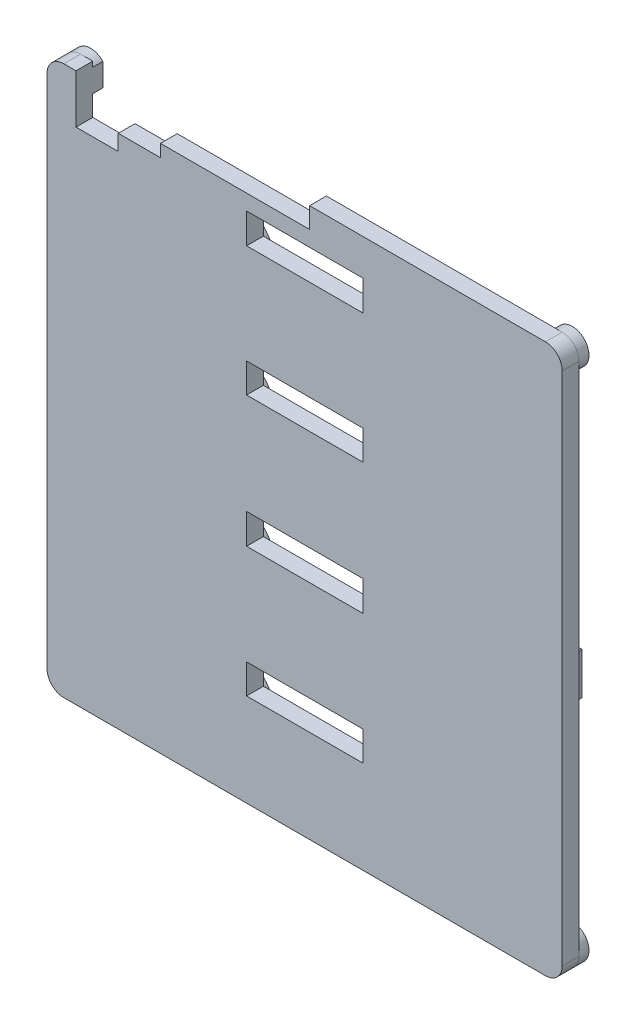
SolidWorks part; units mm, degrees
ref_plane "前视基准面" through (0, 0, 0) normal (0, 0, 1) x (1, 0, 0)
ref_plane "上视基准面" through (0, 0, 0) normal (0, 1, 0) x (1, 0, 0)
ref_plane "右视基准面" through (0, 0, 0) normal (1, 0, 0) x (0, 0, -1)
other "Configuration Table"
ref_plane "基准面1" through (0, 0, -42.5914) normal (0, 0, -1) x (-1, 0, 0)
sketch "草图1" plane through (0, 0, -42.5914) normal (0, 0, -1) x (-1, 0, 0)
  line L20 (41.4092, 120.2374) -> (-102.2385, 120.2373)
  line L21 (-107.2387, 115.2372) -> (-107.2386, -38.4842)
  line L22 (-102.2402, -43.4827) -> (41.4109, -43.4826)
  line L23 (46.4094, -38.4842) -> (46.4093, 115.2372)
  arc A20 (46.4093, 115.2372) -> (41.4092, 120.2374) centre (41.4092, 115.2372) ccw
  arc A21 (-102.2385, 120.2373) -> (-107.2387, 115.2372) centre (-102.2385, 115.2372) ccw
  arc A22 (-107.2386, -38.4842) -> (-102.2402, -43.4827) centre (-102.2402, -38.4842) ccw
  arc A23 (41.4109, -43.4826) -> (46.4094, -38.4842) centre (41.4109, -38.4842) ccw
extrude "凸台-拉伸1" add sketch "草图1" along normal blind 5
sketch "草图3" plane through (0, 0, -47.5914) normal (0, 0, -1) x (-1, 0, 0)
  line L5 (22.0323, 45.3277) -> (11.4184, 45.3277)
  line L6 (22.0323, 45.3277) -> (22.0323, 20.4419)
  line L7 (22.0323, 20.4419) -> (11.4184, 20.4419)
  line L8 (11.4184, 45.3277) -> (11.4184, 20.4419)
  line L9 (-66.1205, 38.2743) -> (-105.0787, 38.2743)
  line L10 (-66.1205, 38.2743) -> (-66.1205, 25.6801)
  line L11 (-66.1205, 25.6801) -> (-105.0787, 25.6801)
  line L12 (-105.0787, 38.2743) -> (-105.0787, 25.6801)
  line L13 (-76.2404, 116.5516) -> (-89.8192, 116.5516)
  line L14 (-76.2404, 116.5516) -> (-76.2404, 82.3988)
  line L15 (-76.2404, 82.3988) -> (-89.8192, 82.3988)
  line L16 (-89.8192, 116.5516) -> (-89.8192, 82.3988)
  line L17 (26.5757, 102.6562) -> (14.4763, 102.6562)
  line L18 (26.5757, 102.6562) -> (26.5757, 79.5664)
  line L19 (26.5757, 79.5664) -> (14.4763, 79.5664)
  line L20 (14.4763, 102.6562) -> (14.4763, 79.5664)
  line L21 (24.3318, -15.6667) -> (16.7254, -15.6667)
  line L22 (24.3318, -15.6667) -> (24.3318, -38.483)
  line L23 (24.3318, -38.483) -> (16.7254, -38.483)
  line L24 (16.7254, -15.6667) -> (16.7254, -38.483)
  line L25 (-76.2404, -15.6667) -> (-87.4137, -15.6667)
  line L26 (-76.2404, -15.6667) -> (-76.2404, -38.483)
  line L27 (-76.2404, -38.483) -> (-87.4137, -38.483)
  line L28 (-87.4137, -15.6667) -> (-87.4137, -38.483)
  circle A0 centre (-3.5966, 93.0119) radius 6.625 construction
  circle A1 centre (-3.581, 54.2036) radius 6.625 construction
  circle A2 centre (-59.0858, 90.0418) radius 6.625 construction
  circle A3 centre (-59.0702, 51.2335) radius 6.625 construction
  circle A4 centre (-59.039, -26.383) radius 6.625 construction
  circle A5 centre (-59.0546, 12.4253) radius 6.625 construction
  circle A6 centre (-3.5654, 15.3953) radius 6.625 construction
  circle A7 centre (-3.5498, -23.413) radius 6.625 construction
  circle A8 centre (-3.5966, 93.0119) radius 6.625 construction
  circle A9 centre (-3.581, 54.2036) radius 6.625 construction
  circle A10 centre (-59.0858, 90.0418) radius 6.625 construction
  circle A11 centre (-59.0702, 51.2335) radius 6.625 construction
  circle A12 centre (-59.039, -26.383) radius 6.625 construction
  circle A13 centre (-59.0546, 12.4253) radius 6.625 construction
  circle A14 centre (-3.5654, 15.3953) radius 6.625 construction
  circle A15 centre (-3.5498, -23.413) radius 6.625 construction
  circle A16 centre (41.4105, 115.237) radius 5
  circle A17 centre (41.4105, 115.237) radius 5
  circle A20 centre (-102.2375, 115.237) radius 2
  circle A21 centre (41.4105, 115.237) radius 2
  circle A22 centre (-102.2375, 115.237) radius 5
  circle A23 centre (-102.2375, 115.237) radius 5
  circle A24 centre (-102.2375, -38.483) radius 5
  circle A25 centre (-102.2375, -38.483) radius 5
  circle A26 centre (41.4105, -38.483) radius 5
  circle A27 centre (41.4105, -38.483) radius 5
  circle A28 centre (-3.5966, 93.0119) radius 9.625
  circle A29 centre (-3.581, 54.2036) radius 9.625
  circle A30 centre (-59.0858, 90.0418) radius 9.625
  circle A31 centre (-59.0702, 51.2335) radius 9.625
  circle A32 centre (-59.039, -26.383) radius 9.625
  circle A33 centre (-59.0546, 12.4253) radius 9.625
  circle A34 centre (-3.5654, 15.3953) radius 9.625
  circle A35 centre (-3.5498, -23.413) radius 9.625
  circle A36 centre (-102.2375, -38.483) radius 2
  circle A37 centre (41.4105, -38.483) radius 2
  dimension "D6" = 3
  dimension "D1" = 2.5
  dimension "D2" = 2.5
  dimension "D3" = 2.5
  dimension "D4" = 2.5
  dimension "D5" = 3
extrude "凸台-拉伸2" add sketch "草图3" along normal up to surface (3 mm away)
sketch "草图4" plane through (0, 0, -42.5914) normal (0, 0, 1) x (1, 0, 0)
  line L0 (-37.7635, 120.8202) -> (-37.7635, 105.691)
  line L1 (13.1152, 109.474) -> (47.8854, 109.474)
  line L2 (13.1152, 109.474) -> (13.1152, 100.474)
  line L3 (13.1152, 100.474) -> (47.8854, 100.474)
  line L4 (47.8854, 109.474) -> (47.8854, 100.474)
  line L5 (13.1152, 70.739) -> (47.8854, 70.739)
  line L6 (13.1152, 70.739) -> (13.1152, 61.939)
  line L7 (13.1152, 61.939) -> (47.8854, 61.939)
  line L8 (47.8854, 70.739) -> (47.8854, 61.939)
  line L9 (13.1152, 31.877) -> (47.8854, 31.877)
  line L10 (13.1152, 31.877) -> (13.1152, 22.877)
  line L11 (13.1152, 22.877) -> (47.8854, 22.877)
  line L12 (47.8854, 31.877) -> (47.8854, 22.877)
  line L13 (13.1152, -6.985) -> (47.8854, -6.985)
  line L14 (13.1152, -6.985) -> (13.1152, -15.785)
  line L15 (13.1152, -15.785) -> (47.8854, -15.785)
  line L16 (47.8854, -6.985) -> (47.8854, -15.785)
  line L18 (-37.7635, 105.691) -> (-25.1635, 105.691)
  line L19 (-25.1635, 105.691) -> (-25.1635, 110.396)
  line L20 (-25.1635, 110.396) -> (-12.5715, 110.396)
  line L21 (-12.5715, 110.396) -> (-12.5715, 114.0907)
  line L22 (-12.5715, 114.0907) -> (31.9075, 114.0907)
  line L23 (31.9075, 114.0907) -> (31.9075, 120.8202)
  line L24 (31.9075, 120.8202) -> (-37.7635, 120.8202)
  point P26 (-37.1915, 120.237)
  point P27 (0, 0)
  point P28 (-37.7635, 120.237)
  dimension "D1" = 1.5
  dimension "D2" = 1.5
  dimension "D3" = 1.5
  dimension "D4" = 1.5
  dimension "D5" = 1.5
  dimension "D6" = 1.5
  dimension "D7" = 1.5
  dimension "D8" = 1.5
  dimension "D9" = 1.5
  dimension "D10" = 1.5
  dimension "D11" = 1.5
  dimension "D12" = 1.5
  dimension "D13" = 1.5
  dimension "D14" = 1.5
  dimension "D15" = 1.5
  dimension "D16" = 1.5
  dimension "D17" = 1.5
extrude "切除-拉伸1" cut sketch "草图4" against normal through all
